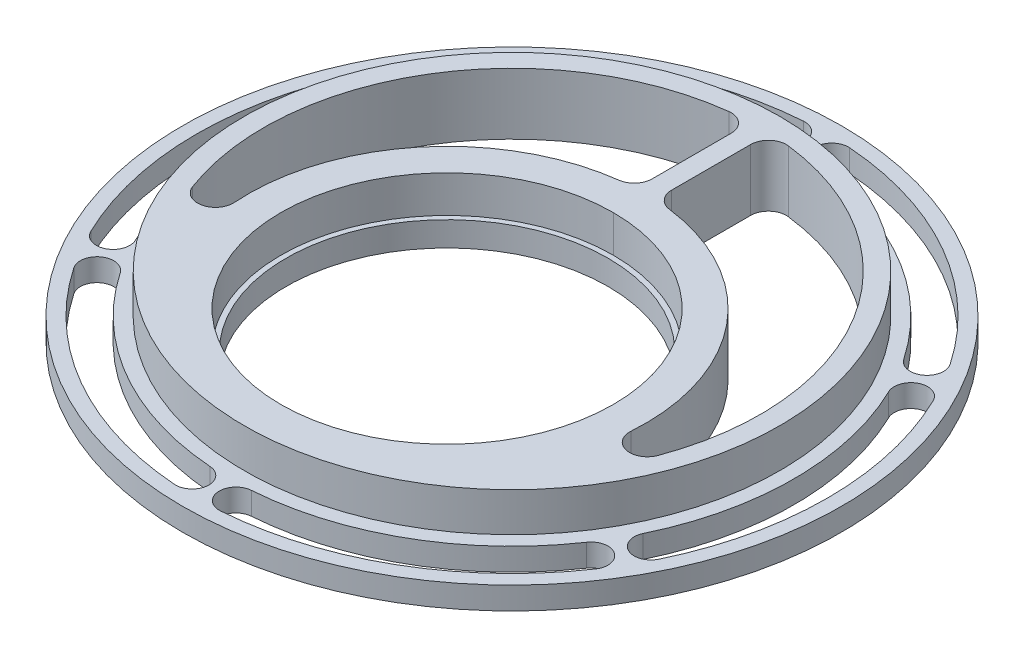
SolidWorks part; units mm, degrees
material "6061-T6 (SS)"
ref_plane "X-Y Datum" through (0, 0, 0) normal (0, 0, 1) x (1, 0, 0)
ref_plane "X-Z Datum" through (0, 0, 0) normal (0, 1, 0) x (1, 0, 0)
ref_plane "Y-Z Datum" through (0, 0, 0) normal (1, 0, 0) x (0, 0, -1)
sketch "Sketch1" plane through (0, 0, 0) normal (0, 1, 0) x (1, 0, 0)
  line L0 (0, 0) -> (0, -12.7) construction
  line L1 (0, -43.0151) -> (0, 43.0151) construction
  line L2 (0, 52.3875) -> (0, 64.4525) construction
  circle A0 centre (0, -12.7) radius 30.988
  circle A1 centre (0, 0) radius 52.3875 construction
  circle A2 centre (0, 0) radius 64.4525
  circle A3 centre (0, 0) radius 58.42 construction
  point P12 (0, 58.42)
  dimension "D2" = 61.976
  dimension "D3" = 104.775
  dimension "D4" = 128.905
  dimension "D5" = 116.84
  dimension "D1" = 12.7
extrude "Slotted-Body Extrude" add sketch "Sketch1" along normal blind 4.191 and the other way blind 0.2032
sketch "Sketch5" plane through (0, 4.191, 0) normal (0, 1, 0) x (1, 0, 0)
  circle A0 centre (0, 0) radius 52.3875 construction
  circle A1 centre (0, 0) radius 52.3875
extrude "Boss-Extrude3" add sketch "Sketch5" along normal blind 7.62
sketch "Sketch6" plane through (0, -0.2032, 0) normal (0, -1, 0) x (1, 0, 0)
  line L0 (0, -79.2756) -> (0, 0) construction
  circle A0 centre (0, 12.7) radius 30.988 construction
  circle A1 centre (0, 12.7) radius 30.988 construction
  circle A2 centre (0, 12.7) radius 32.512
  circle A21 centre (0, 0) radius 64.4525 construction
  dimension "D1" = 65.024
extrude "Cut-Extrude5" cut sketch "Sketch6" against normal through all
sketch "Sketch8" plane through (0, -0.2032, 0) normal (0, -1, 0) x (1, 0, 0)
  circle A0 centre (0, 12.7) radius 32.512 construction
  circle A1 centre (0, 12.7) radius 32.512
  circle A2 centre (0, 12.7) radius 31.496
  dimension "D1" = 62.992
extrude "Boss-Extrude4" add sketch "Sketch8" against normal blind 4.795 separate body
ref_point "Point1"
ref_plane "Plane1" through (0, 0, 0) normal (1, 0, 0) x (0, 0, -1)
split line "Split Line1"
sketch "Sketch11" plane through (0, -0.2032, 0) normal (0, -1, 0) x (1, 0, 0)
  line L1 (-64.4525, -64.4525) -> (64.4525, -64.4525)
  line L2 (-64.4525, -64.4525) -> (-64.4525, 64.4525)
  line L3 (-64.4525, 64.4525) -> (64.4525, 64.4525)
  line L4 (64.4525, -64.4525) -> (64.4525, 64.4525)
  line L5 (-64.4525, -64.4525) -> (64.4525, 64.4525) construction
  line L6 (-64.4525, 64.4525) -> (64.4525, -64.4525) construction
  circle A0 centre (0, 0) radius 64.4525 construction
  point P0 (0, 0)
ref_point "Point6"
sketch "Sketch12" plane through (0, 4.191, 0) normal (0, 1, 0) x (1, 0, 0)
  line L0 (0, 0) -> (-1.0196, -58.4111) construction
  line L1 (0, 0) -> (-50.0757, -30.0885) construction
  line L2 (0, 0) -> (0, -64.4525) construction
  arc A3 (-50.0757, -30.0885) -> (-1.0196, -58.4111) centre (0, 0) ccw construction
  arc A10 (-51.0166, -34.6728) -> (-4.5192, -61.5181) centre (0, 0) ccw
  arc A15 (-45.6177, -31.0035) -> (-4.041, -55.0079) centre (0, 0) ccw
  arc A20 (-45.6177, -31.0035) -> (-51.0166, -34.6728) centre (-48.3172, -32.8382) ccw
  arc A25 (-52.8734, -31.7696) -> (-1.0765, -61.6745) centre (0, 0) ccw construction
  arc A30 (-47.278, -28.4075) -> (-0.9626, -55.1477) centre (0, 0) ccw construction
  arc A35 (-4.5192, -61.5181) -> (-4.041, -55.0079) centre (-4.2801, -58.263) ccw
  circle A40 centre (0, 0) radius 64.4525 construction
  arc A45 (-55.5359, -26.8453) -> (-49.6587, -24.0043) centre (-52.5973, -25.4248) ccw
  arc A50 (-49.6587, 24.0043) -> (-49.6587, -24.0043) centre (0, 0) ccw
  arc A55 (-49.6587, 24.0043) -> (-55.5359, 26.8453) centre (-52.5973, 25.4248) ccw
  arc A56 (-55.5359, 26.8453) -> (-55.5359, -26.8453) centre (0, 0) ccw
  arc A57 (-51.0166, 34.6728) -> (-45.6177, 31.0035) centre (-48.3172, 32.8382) ccw
  arc A58 (-4.041, 55.0079) -> (-45.6177, 31.0035) centre (0, 0) ccw
  arc A59 (-4.041, 55.0079) -> (-4.5192, 61.5181) centre (-4.2801, 58.263) ccw
  arc A60 (-4.5192, 61.5181) -> (-51.0166, 34.6728) centre (0, 0) ccw
  arc A61 (4.5192, 61.5181) -> (4.041, 55.0079) centre (4.2801, 58.263) ccw
  arc A62 (45.6177, 31.0035) -> (4.041, 55.0079) centre (0, 0) ccw
  arc A63 (45.6177, 31.0035) -> (51.0166, 34.6728) centre (48.3172, 32.8382) ccw
  arc A64 (51.0166, 34.6728) -> (4.5192, 61.5181) centre (0, 0) ccw
  arc A65 (55.5359, 26.8453) -> (49.6587, 24.0043) centre (52.5973, 25.4248) ccw
  arc A66 (49.6587, -24.0043) -> (49.6587, 24.0043) centre (0, 0) ccw
  arc A67 (49.6587, -24.0043) -> (55.5359, -26.8453) centre (52.5973, -25.4248) ccw
  arc A68 (55.5359, -26.8453) -> (55.5359, 26.8453) centre (0, 0) ccw
  arc A69 (51.0166, -34.6728) -> (45.6177, -31.0035) centre (48.3172, -32.8382) ccw
  arc A70 (4.041, -55.0079) -> (45.6177, -31.0035) centre (0, 0) ccw
  arc A71 (4.041, -55.0079) -> (4.5192, -61.5181) centre (4.2801, -58.263) ccw
  arc A72 (4.5192, -61.5181) -> (51.0166, -34.6728) centre (0, 0) ccw
  point P57 (0, 0)
  dimension "D1" = 116.84
  dimension "D2" = 58
  dimension "D5" = 1
  dimension "D3" = 3.2639
  dimension "D4" = 3.2639
sketch "Sketch16" plane through (0, 11.811, 0) normal (0, 1, 0) x (1, 0, 0)
  line L0 (0, 0) -> (0, 48.5775) construction
  line L4 (1.905, 44.7607) -> (1.905, 29.3092)
  line L5 (-1.905, 44.7607) -> (-1.905, 29.3092)
  arc A22 (45.517, -16.9698) -> (5.8156, 48.2281) centre (0, 0) ccw
  circle A23 centre (0, -12.7) radius 32.512 construction
  arc A24 (38.7611, -15.4983) -> (4.9524, 25.8451) centre (0, -12.7) ccw
  arc A25 (-38.7611, -15.4983) -> (-45.517, -16.9698) centre (-42.2446, -15.7497) cw
  arc A28 (45.517, -16.9698) -> (38.7611, -15.4983) centre (42.2446, -15.7497) cw
  circle A31 centre (0, 0) radius 52.3875 construction
  arc A32 (-5.8156, 48.2281) -> (-45.517, -16.9698) centre (0, 0) ccw
  arc A33 (-4.9524, 25.8451) -> (-38.7611, -15.4983) centre (0, -12.7) ccw
  arc A39 (4.9524, 25.8451) -> (1.905, 29.3092) centre (5.3975, 29.3092) cw
  arc A45 (1.905, 44.7607) -> (5.8156, 48.2281) centre (5.3975, 44.7607) cw
  arc A46 (-4.9524, 25.8451) -> (-1.905, 29.3092) centre (-5.3975, 29.3092) ccw
  arc A47 (-1.905, 44.7607) -> (-5.8156, 48.2281) centre (-5.3975, 44.7607) ccw
  point P18 (1.905, 26.1153)
  point P21 (1.905, 48.5401)
  point P24 (-1.905, 26.1153)
  point P27 (-1.905, 48.5401)
  dimension "D1" = 3.4925
  dimension "D2" = 3.4925
  dimension "D3" = 65.024
  dimension "D4" = 6.35
  dimension "D5" = 3.81
  dimension "D6" = 1.905
  dimension "D7" = 3.4925
extrude "Cut-Extrude6" cut sketch "Sketch16" against normal through all contours L5 A47 A32 A25 A33 A46 | A45 L4 A39 A24 A28 A22 | A46 L5 A47 A32 A25 A33 region at (27.5566, 11.811, -21.5451) region at (-27.5566, 11.811, -21.5451)
extrude "Cut-Extrude7" cut sketch "Sketch12" against normal through all
